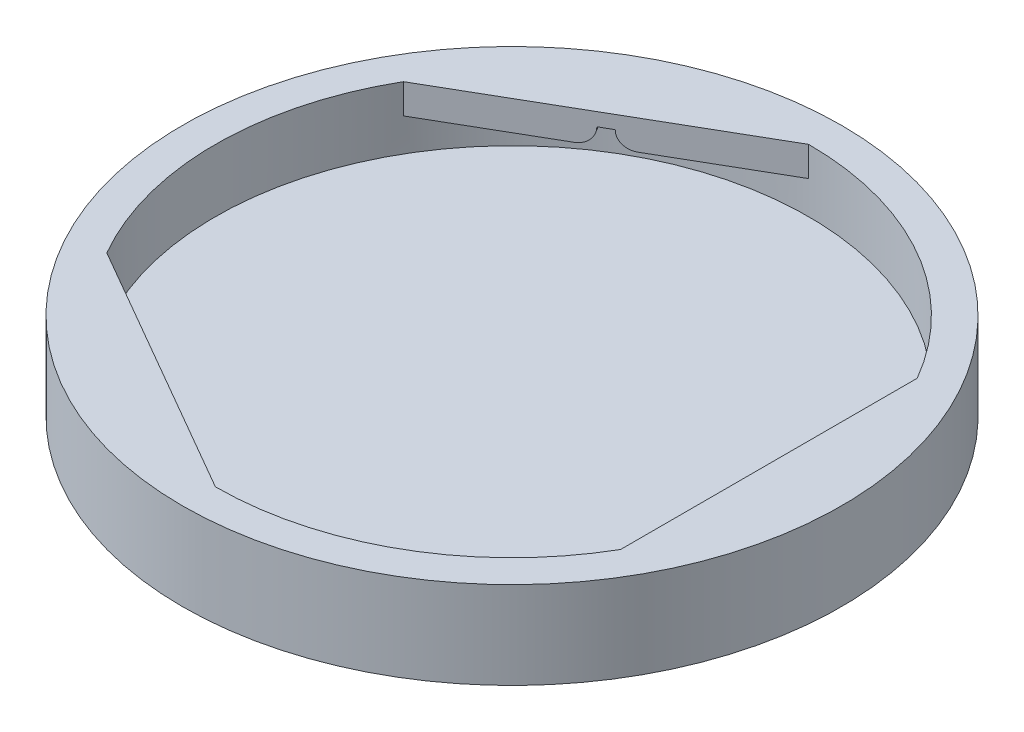
SolidWorks part; units mm, degrees
ref_plane "Front" through (0, 0, 0) normal (0, 0, 1) x (1, 0, 0)
ref_plane "Top" through (0, 0, 0) normal (0, 1, 0) x (1, 0, 0)
ref_plane "Right" through (0, 0, 0) normal (1, 0, 0) x (0, 0, -1)
sketch "Sketch1" plane through (0, 0, 0) normal (0, 1, 0) x (1, 0, 0)
  circle A0 centre (0, 0) radius 20
extrude "Boss-Extrude1" add sketch "Sketch1" along normal blind 1.5
sketch "Sketch2" plane through (0, 1.5, 0) normal (0, 1, 0) x (1, 0, 0)
  circle A0 centre (0, 0) radius 20
  circle A1 centre (0, 0) radius 18
extrude "Boss-Extrude2" add sketch "Sketch2" along normal blind 2
sketch "Sketch3" plane through (0, 3.5, 0) normal (0, 1, 0) x (1, 0, 0)
  line L6 (-15.5885, 9) -> (0, 18)
  line L7 (15.5885, 9) -> (15.5885, -9)
  line L8 (-15.5885, -9) -> (0, -18)
  circle A0 centre (0, 0) radius 20
  arc A1 (-15.5885, 9) -> (-15.5885, -9) centre (0, 0) ccw
  arc A2 (15.5885, 9) -> (0, 18) centre (0, 0) ccw
  arc A3 (0, -18) -> (15.5885, -9) centre (0, 0) ccw
  point P12 (0, 0)
extrude "Boss-Extrude3" add sketch "Sketch3" along normal blind 1.8
ref_plane "Plane1" through (0, 3.5, 0) normal (0, 1, 0) x (1, 0, 0)
sketch "Sketch4" plane through (0, 3.5, 0) normal (0, 1, 0) x (1, 0, 0)
  line L0 (0, 0) -> (-7.7942, 13.5) construction
  line L1 (0, 18) -> (-15.5885, 9) construction
  line L2 (-8.0987, 13.2159) -> (-9.405, 15.3475)
  line L3 (-7.396, 13.6217) -> (-8.5889, 15.8187)
  arc A0 (-8.5889, 15.8187) -> (-9.405, 15.3475) centre (0, 0) ccw
  arc A1 (-7.396, 13.6217) -> (-8.0987, 13.2159) centre (0, 0) ccw
  dimension "D1" = 1.5
extrude "Cut-Extrude1" cut sketch "Sketch4" along normal blind 1
fillet "Fillet2" radius 1 2 edges at (-8.0148, 3.5, -14.7614) (-8.7764, 3.5, -14.3217) first distance on face at (-8.0148, 4, -14.7614) first distance on face at (-8.7764, 4, -14.3217)
pattern_circular "CirPattern1" count 3 over 360 about axis through (0, 5.3, 0) along (0, 1, 0) of "Cut-Extrude1", "Fillet2"
